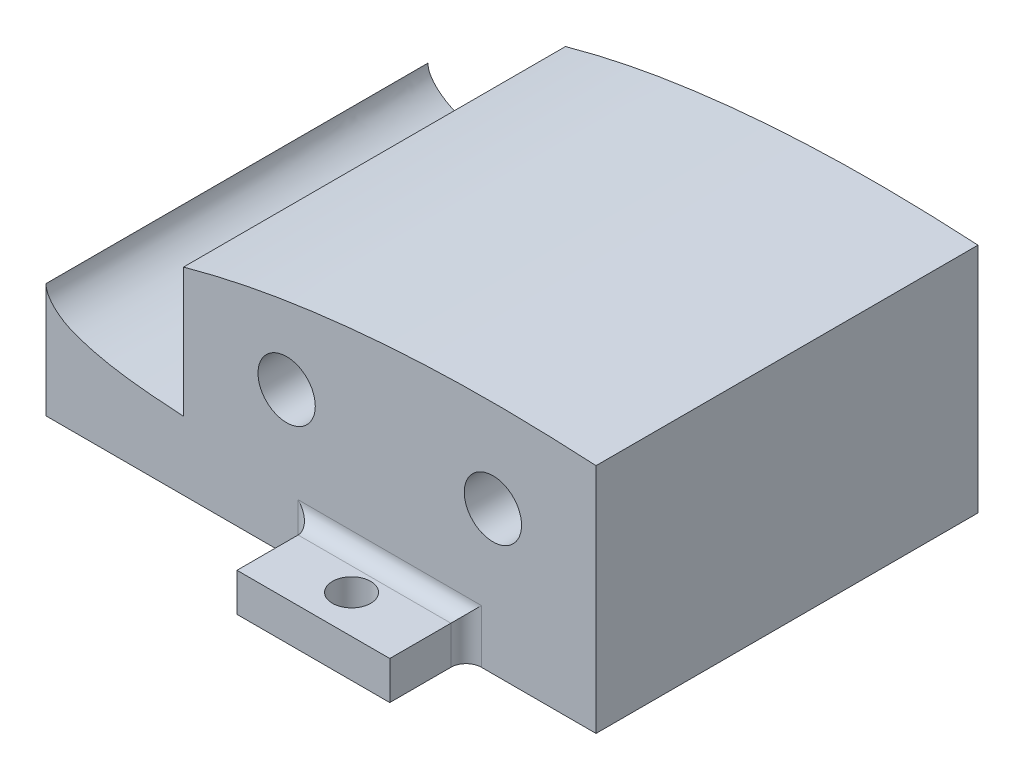
SolidWorks part; units mm, degrees
ref_plane "Front Plane" through (0, 0, 0) normal (0, 0, 1) x (1, 0, 0)
ref_plane "Top Plane" through (0, 0, 0) normal (0, 1, 0) x (1, 0, 0)
ref_plane "Right Plane" through (0, 0, 0) normal (1, 0, 0) x (0, 0, -1)
curve "Curve1"
  spline degree 3 poles (25.4, 0.033, 0) (24.9771, 0.1481, 0) (24.1334, 0.3778, 0) (22.4431, 0.7955, 0) (20.3293, 1.2569, 0) (17.7869, 1.7118, 0) (15.2464, 2.0846, 0) (12.7045, 2.3505, 0) (10.1628, 2.5164, 0) (8.041, 2.5181, 0) (6.3469, 2.4009, 0) (5.0745, 2.2465, 0) (3.7995, 2.0188, 0) (2.7428, 1.745, 0) (1.8961, 1.4685, 0) (1.2577, 1.2074, 0) (0.7129, 0.9251, 0) (0.2401, 0.5874, 0) (-0.1715, 0.0442, 0) (0.2727, -0.3711, 0) (0.7261, -0.5342, 0) (1.266, -0.6443, 0) (1.9036, -0.7002, 0) (2.7513, -0.7398, 0) (3.8103, -0.7368, 0) (5.0806, -0.7013, 0) (6.3499, -0.6336, 0) (8.0433, -0.5544, 0) (10.1596, -0.4528, 0) (12.7001, -0.3574, 0) (15.2397, -0.2514, 0) (17.7796, -0.1611, 0) (20.3198, -0.0947, 0) (22.4366, -0.061, 0) (24.13, -0.0388, 0) (24.9767, -0.035, 0) (25.4, -0.033, 0) knots 0 0 0 0 0.025305 0.050488 0.10052 0.150191 0.199587 0.24874 0.297716 0.346601 0.371103 0.395726 0.42057 0.445825 0.458702 0.47192 0.485786 0.493461 0.506863 0.516148 0.522766 0.535269 0.547551 0.559786 0.584229 0.608681 0.633151 0.657622 0.706558 0.755482 0.804406 0.85332 0.902221 0.951113 0.975557 1 1 1 1
sketch "Original NACA 4412" plane through (0, 0, 0) normal (0, 0, 1) x (1, 0, 0)
  line L0 (25.4, 0.033) -> (25.4, -0.033)
  spline S0 degree 3 poles (623.3011, 1907.6527) (79.6214, -43.1606) (55.117, -7.2775) (22.4431, 0.7955) (20.3293, 1.2569) (17.7869, 1.7118) (15.2464, 2.0846) (12.7045, 2.3505) (10.1628, 2.5164) (8.041, 2.5181) (6.3469, 2.4009) (5.0745, 2.2465) (3.7995, 2.0188) (2.7428, 1.745) (1.8961, 1.4685) (1.2577, 1.2074) (0.7129, 0.9251) (0.2401, 0.5874) (-0.1715, 0.0442) (0.2727, -0.3711) (0.7261, -0.5342) (1.266, -0.6443) (1.9036, -0.7002) (2.7513, -0.7398) (3.8103, -0.7368) (5.0806, -0.7013) (6.3499, -0.6336) (8.0433, -0.5544) (10.1596, -0.4528) (12.7001, -0.3574) (15.2397, -0.2514) (17.7796, -0.1611) (20.3198, -0.0947) (22.4366, -0.061) (67.8901, 0.5348) (112.6717, -18.929) (139.2928, 1995.2022) knots -1.842584 -1.842584 -1.842584 -1.842584 0.025305 0.050488 0.10052 0.150191 0.199587 0.24874 0.297716 0.346601 0.371103 0.395726 0.42057 0.445825 0.458702 0.47192 0.485786 0.493461 0.506863 0.516148 0.522766 0.535269 0.547551 0.559786 0.584229 0.608681 0.633151 0.657622 0.706558 0.755482 0.804406 0.85332 0.902221 0.951113 0.975557 3.526814 3.526814 3.526814 3.526814 only from (25.4, 0.033) to (25.4, -0.033) construction
  spline S1 degree 3 poles (25.4, 0.033) (24.9771, 0.1481) (24.1334, 0.3778) (22.4431, 0.7955) (20.3293, 1.2569) (17.7869, 1.7118) (15.2464, 2.0846) (12.7045, 2.3505) (10.1628, 2.5164) (8.041, 2.5181) (6.3469, 2.4009) (5.0745, 2.2465) (3.7995, 2.0188) (2.7428, 1.745) (1.8961, 1.4685) (1.2577, 1.2074) (0.7129, 0.9251) (0.2401, 0.5874) (-0.1715, 0.0442) (0.2727, -0.3711) (0.7261, -0.5342) (1.266, -0.6443) (1.9036, -0.7002) (2.7513, -0.7398) (3.8103, -0.7368) (5.0806, -0.7013) (6.3499, -0.6336) (8.0433, -0.5544) (10.1596, -0.4528) (12.7001, -0.3574) (15.2397, -0.2514) (17.7796, -0.1611) (20.3198, -0.0947) (22.4366, -0.061) (24.13, -0.0388) (24.9767, -0.035) (25.4, -0.033) knots 0 0 0 0 0.025305 0.050488 0.10052 0.150191 0.199587 0.24874 0.297716 0.346601 0.371103 0.395726 0.42057 0.445825 0.458702 0.47192 0.485786 0.493461 0.506863 0.516148 0.522766 0.535269 0.547551 0.559786 0.584229 0.608681 0.633151 0.657622 0.706558 0.755482 0.804406 0.85332 0.902221 0.951113 0.975557 1 1 1 1
sketch "Scaled and rotated by 1.5°" plane through (0, 0, 0) normal (0, 0, 1) x (1, 0, 0)
  line L0 (228.6156, -6.2198) -> (228.6, -6.8141)
  line L1 (40.005, 17.5068) -> (40.005, -8.0377) construction
  line L2 (0, 2.8493) -> (0, 0) construction
  line L3 (40.005, 4.7346) -> (74.295, 4.7346) construction
  line L4 (74.295, 4.7346) -> (40.005, 4.7346) construction
  line L5 (228.6, -6.8141) -> (228.6, -6.2434) construction
  circle A0 centre (40.005, 4.7346) radius 4.7625
  circle A1 centre (74.295, 4.7346) radius 4.7625
  spline S1 degree 3 poles (228.6156, -6.2198) (224.8373, -5.0843) (217.299, -2.8187) (202.1877, 1.3376) (183.276, 5.9878) (160.5054, 10.6799) (137.7331, 14.6335) (114.9229, 17.6255) (92.0911, 19.717) (72.9986, 20.2321) (57.7264, 19.5766) (46.2411, 18.4872) (34.7139, 16.739) (25.1416, 14.5242) (17.4573, 12.2353) (11.6508, 10.0367) (6.6824, 7.6245) (2.3479, 4.6971) (-1.484, -0.0934) (2.416, -3.9359) (6.457, -5.51) (11.2894, -6.6275) (17.0139, -7.2813) (24.6323, -7.8374) (34.1618, -8.0602) (45.6007, -8.0396) (57.039, -7.7297) (72.295, -7.4161) (91.3623, -7.0002) (114.245, -6.7401) (137.1228, -6.385) (159.999, -6.1713) (182.8715, -6.1724) (201.9277, -6.3679) (217.1704, -6.5672) (224.7902, -6.7318) (228.6, -6.8141) knots 0 0 0 0 0.025305 0.050488 0.10052 0.150191 0.199587 0.24874 0.297716 0.346601 0.371103 0.395726 0.42057 0.445825 0.458702 0.47192 0.485786 0.493461 0.506863 0.516148 0.522766 0.535269 0.547551 0.559786 0.584229 0.608681 0.633151 0.657622 0.706558 0.755482 0.804406 0.85332 0.902221 0.951113 0.975557 1 1 1 1
  dimension "D2" = 9.525
  dimension "D1" = 40.005
  dimension "D3" = 34.29
  dimension "D5" = 228.6
  dimension "D4" = 1.5
sketch "Sketch6" plane through (0, 0, 0) normal (0, 0, 1) x (1, 0, 0)
  line L1 (40.005, 17.5068) -> (40.005, -8.0377) construction
  line L2 (0, 2.2821) -> (0, 0) construction
  line L3 (40.005, 4.7346) -> (74.295, 4.7346) construction
  line L4 (74.295, 4.7346) -> (40.005, 4.7346) construction
  line L6 (0, 0) -> (0, -19.05)
  line L7 (0, -19.05) -> (91.44, -19.05)
  line L8 (91.44, -19.05) -> (91.44, 19.5089)
  line L9 (22.86, -7.6743) -> (22.86, 13.8098)
  circle A0 centre (40.005, 4.7346) radius 4.7625
  circle A1 centre (74.295, 4.7346) radius 4.7625
  spline S0 degree 3 poles (0, 0) (0, -0.1787) (0.1349, -1.6884) (2.416, -3.9359) (6.457, -5.51) (11.2894, -6.6275) (17.0139, -7.2813) (20.8709, -7.5628) (22.818, -7.672) (22.86, -7.6743) knots 0.505626 0.505626 0.505626 0.505626 0.506863 0.516148 0.522766 0.535269 0.547551 0.559786 0.560056 0.560056 0.560056 0.560056
  spline S2 degree 3 poles (91.44, 19.5089) (84.0356, 19.9341) (72.792, 20.2232) (57.7264, 19.5766) (46.2411, 18.4872) (34.7139, 16.739) (26.9508, 14.9428) (23.0064, 13.8507) (22.86, 13.8098) knots 0.299041 0.299041 0.299041 0.299041 0.346601 0.371103 0.395726 0.42057 0.445825 0.446799 0.446799 0.446799 0.446799
  dimension "D2" = 9.525
  dimension "D1" = 40.005
  dimension "D3" = 34.29
  dimension "D6" = 91.44
  dimension "D7" = 22.86
  dimension "D4" = 19.05
extrude "Boss-Extrude2" add sketch "Sketch6" along normal blind 31.75 and the other way blind 31.75
sketch "Sketch7" plane through (0, -19.05, 0) normal (0, -1, 0) x (1, 0, 0)
  line L0 (0, 31.75) -> (91.44, 31.75) construction
  line L1 (44.45, 31.75) -> (69.85, 31.75)
  line L2 (44.45, 31.75) -> (44.45, 44.45)
  line L3 (44.45, 44.45) -> (69.85, 44.45)
  line L4 (69.85, 31.75) -> (69.85, 44.45)
  line L5 (57.15, 44.45) -> (57.15, 31.75) construction
  line L6 (0, 0) -> (35.4889, 0) construction
  line L7 (57.15, -44.45) -> (57.15, -31.75) construction
  line L8 (69.85, -31.75) -> (69.85, -44.45)
  line L9 (44.45, -44.45) -> (69.85, -44.45)
  line L10 (44.45, -31.75) -> (44.45, -44.45)
  line L11 (44.45, -31.75) -> (69.85, -31.75)
  circle A0 centre (57.15, 38.1) radius 3.175
  circle A1 centre (57.15, -38.1) radius 3.175
  point P6 (57.15, 44.45)
  dimension "D4" = 6.35
  dimension "D1" = 57.15
  dimension "D2" = 12.7
  dimension "D5" = 38.1
extrude "Boss-Extrude3" add sketch "Sketch7" against normal blind 6.35
fillet "Fillet2" radius 2.54 6 edges at (57.15, -12.7, 31.75) (44.45, -15.875, 31.75) (69.85, -15.875, 31.75) (57.15, -12.7, -31.75) (69.85, -15.875, -31.75) (44.45, -15.875, -31.75)
equation "\"span\"= 48"
equation "\"wing_chord\"= 9"
equation "\"fuse_len\"= 15"
equation "\"fuse_height\"= 5"
equation "\"fuse_wid\"= 5"
equation "\"foam_t\"= 0.1875"
equation "\"main_spar_len\"= 36"
equation "\"x_fuse_to_wing\"= 3"
equation "\"x_cg_from_le\"= 2.25"
equation "\"boom_len\"= 30"
equation "\"wing_angle\"= 1.5"
equation "\"boom_d\"= 0.75"
equation "\"wing_spar_d\"= 0.375"
equation "\"wing_spar_l\"= 48"
equation "\"wing_spar_spacing\"= 1.35"
equation "\"wing_mount_l\"= 2.5"
equation "\"vstab_span\"= 6.5"
equation "\"hstab_span\"= 15.25"
equation "\"tail_chord\"= 5"
equation "\"D1@Scaled and rotated by 1.5°\"= \"x_cg_from_le\" - \"wing_spar_spacing\"/2"
equation "\"D2@Scaled and rotated by 1.5°\"= \"wing_spar_d\""
equation "\"D3@Scaled and rotated by 1.5°\"=\"wing_spar_spacing\""
equation "\"D5@Scaled and rotated by 1.5°\"= \"wing_chord\""
equation "\"D3@Sketch6\"= \"wing_spar_spacing\""
equation "\"D1@Sketch6\"=\"x_cg_from_le\" - \"wing_spar_spacing\"/2"
equation "\"D6@Sketch6\"= \"wing_chord\"*0.4"
equation "\"D7@Sketch6\"= \"x_cg_from_le\"-\"wing_spar_spacing\""
equation "\"D1@Sketch7\"= \"x_cg_from_le\""
equation "\"D2@Boss-Extrude2\"= \"wing_mount_l\"/2"
equation "\"D1@Boss-Extrude2\"= \"wing_mount_l\"/2"
equation "\"wing_mount_bolt_spacing\"= \"wing_mount_l\" + 0.5"
equation "\"boom_mount_l\"= 1"
equation "\"D5@Sketch7\"= \"wing_mount_bolt_spacing\"/2"
equation "\"wing_spar_ID\"= 0.25"
equation "\"D2@Sketch6\"= \"wing_spar_d\""
